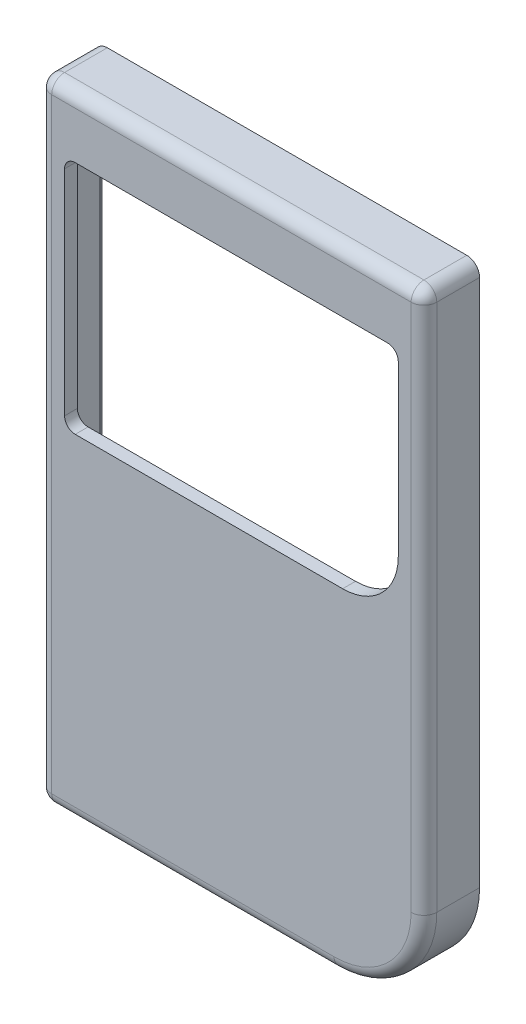
SolidWorks part; units mm, degrees
ref_plane "Front Plane" through (0, 0, 0) normal (0, 0, 1) x (1, 0, 0)
ref_plane "Top Plane" through (0, 0, 0) normal (0, 1, 0) x (1, 0, 0)
ref_plane "Right Plane" through (0, 0, 0) normal (1, 0, 0) x (0, 0, -1)
sketch "Sketch1" plane through (0, 0, 0) normal (0, 0, 1) x (1, 0, 0)
  line L1 (-45, -73.75) -> (45, -73.75)
  line L2 (-45, -73.75) -> (-45, 73.75)
  line L3 (-45, 73.75) -> (45, 73.75)
  line L4 (45, -73.75) -> (45, 73.75)
  line L5 (-45, -73.75) -> (45, 73.75) construction
  line L6 (-45, 73.75) -> (45, -73.75) construction
  point P0 (0, 0)
  dimension "D1" = 90
  dimension "D2" = 147.5
extrude "Boss-Extrude1" add sketch "Sketch1" along normal blind 13
fillet "Rounded Bottom Corner" radius 21 1 edges at (45, -73.75, 6.5)
fillet "Round Edges" radius 3 8 edges at (-10.5, -73.75, 13) (38.8492, -67.5992, 13) (-45, 0, 13) (45, 10.5, 13) (0, 73.75, 13) (-45, -73.75, 6.5) (-45, 73.75, 6.5) (45, 73.75, 6.5)
shell "Shell2" thickness 3 removed face at (-1.784, 1.784, 0)
sketch "Sketch2" plane through (0, 0, 13) normal (0, 0, 1) x (1, 0, 0)
  line L0 (45, 73.75) -> (-45, 73.75) construction
  line L1 (-36.5, 59.75) -> (36.5, 59.75)
  line L2 (-39, 57.25) -> (-39, 7.25)
  line L3 (-36.5, 4.75) -> (26, 4.75)
  line L4 (39, 57.25) -> (39, 17.75)
  line L5 (45, -73.75) -> (45, 73.75) construction
  line L6 (0, -7.15) -> (0, 7.15) construction
  arc A0 (-39, 7.25) -> (-36.5, 4.75) centre (-36.5, 7.25) ccw
  arc A1 (36.5, 59.75) -> (39, 57.25) centre (36.5, 57.25) cw
  arc A2 (-36.5, 59.75) -> (-39, 57.25) centre (-36.5, 57.25) ccw
  arc A3 (26, 4.75) -> (39, 17.75) centre (26, 17.75) ccw
  point P8 (0, 59.75)
  point P11 (0, 0)
  dimension "D4" = 2.5
  dimension "D5" = 13
  dimension "D1" = 14
  dimension "D2" = 6
  dimension "D3" = 55
extrude "Cut-Extrude1" cut sketch "Sketch2" against normal through all
sketch "Sketch3" plane through (0, 0, 0) normal (0, 0, -1) x (-1, 0, 0)
  line L0 (-42, -52.75) -> (-42, 70.75) construction
  line L1 (-42, 70.75) -> (42, 70.75) construction
  line L2 (42, -70.75) -> (42, 70.75) construction
  line L3 (-24, -70.75) -> (42, -70.75) construction
  line L4 (-42, -52.75) -> (-42, 70.75)
  line L5 (-42, 70.75) -> (42, 70.75)
  line L6 (42, -70.75) -> (42, 70.75)
  line L7 (-24, -70.75) -> (42, -70.75)
  line L8 (-43.25, -52.75) -> (-43.25, 72)
  line L9 (-43.25, 72) -> (43.25, 72)
  line L10 (43.25, -72) -> (43.25, 72)
  line L11 (-24, -72) -> (43.25, -72)
  arc A0 (-42, -52.75) -> (-24, -70.75) centre (-24, -52.75) ccw construction
  arc A1 (-42, -52.75) -> (-24, -70.75) centre (-24, -52.75) ccw
  arc A2 (-43.25, -52.75) -> (-24, -72) centre (-24, -52.75) ccw
  dimension "D1" = 1.25
extrude "Cut-Extrude2" cut sketch "Sketch3" against normal blind 1.75
sketch "Sketch4" plane through (0, -73.75, 0) normal (0, -1, 0) x (1, 0, 0)
  line L0 (-3.5, 0) -> (3.5, 0)
  line L1 (-42, 0) -> (24, 0) construction
  line L2 (-3.5, 0) -> (-3.5, 4)
  line L3 (3.5, 0) -> (3.5, 4)
  arc A0 (-3.5, 4) -> (3.5, 4) centre (0, 4) cw
  point P6 (0, 0)
  dimension "D1" = 7
  dimension "D2" = 4
extrude "Cut-Extrude3" cut sketch "Sketch4" against normal up to next
